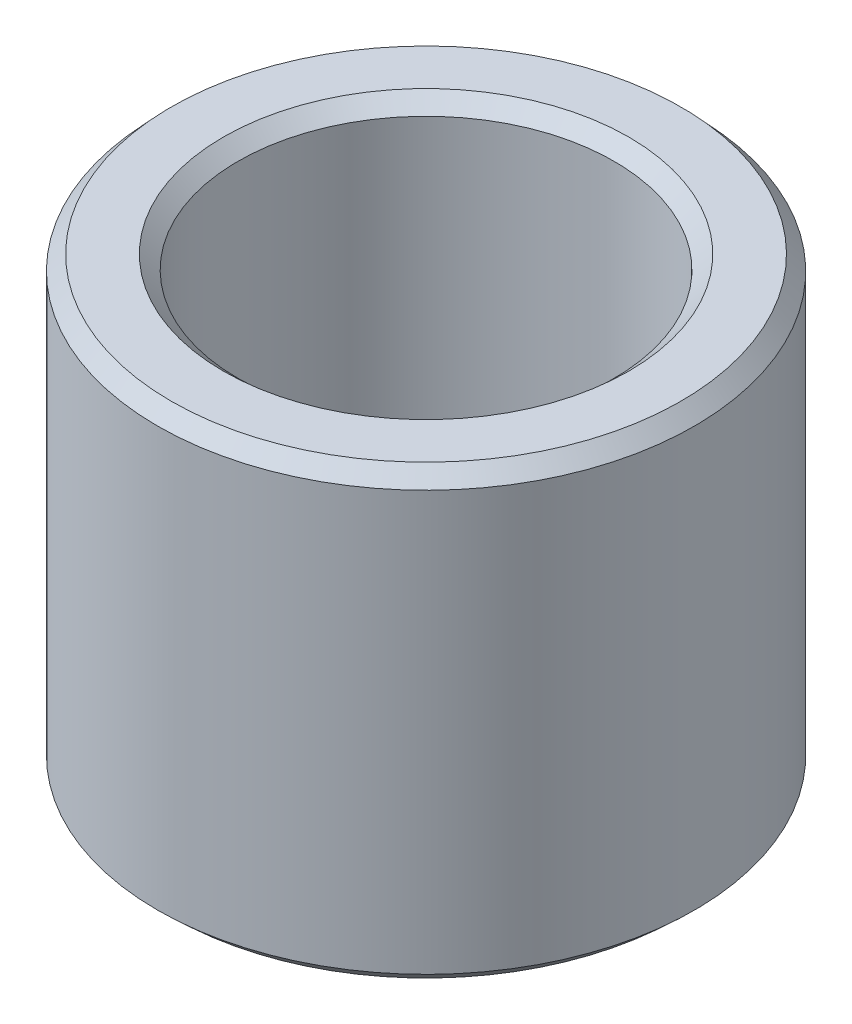
SolidWorks part; units mm, degrees
ref_plane "Front Plane" through (0, 0, 0) normal (0, 0, 1) x (1, 0, 0)
ref_plane "Top Plane" through (0, 0, 0) normal (0, 1, 0) x (1, 0, 0)
ref_plane "Right Plane" through (0, 0, 0) normal (1, 0, 0) x (0, 0, -1)
sketch "Sketch1" plane through (0, 0, 0) normal (0, 1, 0) x (1, 0, 0)
  circle A0 centre (0, 0) radius 60
  dimension "SLEEVE_OD" = 120
extrude "Boss-Extrude1" add sketch "Sketch1" along normal blind 100.0266
sketch "Sketch2" plane through (0, 0, 0) normal (0, 1, 0) x (1, 0, 0)
  circle A0 centre (0, 0) radius 42.0259
  dimension "BORE_D" = 84.0518
extrude "Cut-Extrude1" cut sketch "Sketch2" along normal through all
chamfer "Chamfer1" distance 3.2888 angle 42.749 4 edges at (0, 100.0266, 42.0259) (0, 0, 42.0259) (0, 0, 60) (0, 100.0266, 60) first distance on face at (0, 100.0266, 42.0259) first distance on face at (0, 0, 42.0259) first distance on face at (0, 100.0266, 60)
